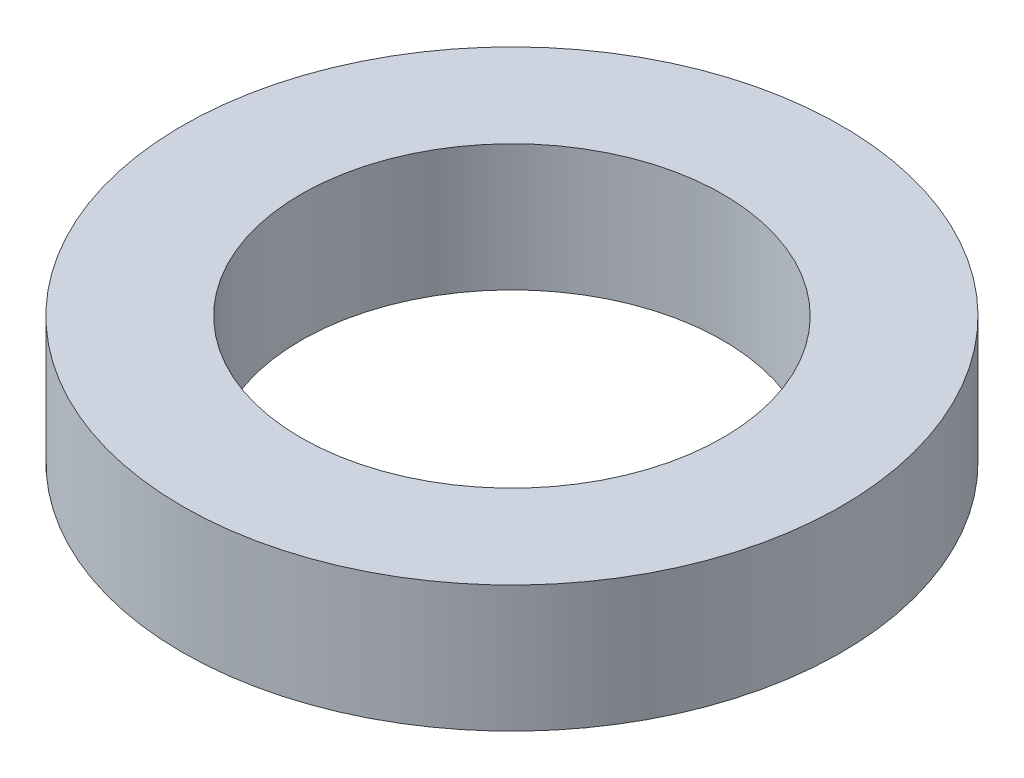
SolidWorks part; units mm, degrees
ref_plane "Front Plane" through (0, 0, 0) normal (0, 0, 1) x (1, 0, 0)
ref_plane "Top Plane" through (0, 0, 0) normal (0, 1, 0) x (1, 0, 0)
ref_plane "Right Plane" through (0, 0, 0) normal (1, 0, 0) x (0, 0, -1)
sketch "Sketch1" plane through (0, 0, 0) normal (0, 1, 0) x (1, 0, 0)
  circle A0 centre (0, 0) radius 62.5
  dimension "FLANGE_OD" = 125
extrude "Boss-Extrude1" add sketch "Sketch1" along normal blind 24
sketch "Sketch2" plane through (0, 0, 0) normal (0, 1, 0) x (1, 0, 0)
  circle A0 centre (0, 0) radius 40
  dimension "BORE_D" = 80
extrude "Cut-Extrude1" cut sketch "Sketch2" along normal through all
sketch "Sketch3" plane through (0, 24, 0) normal (0, 1, 0) x (1, 0, 0)
  circle A0 centre (0, 0) radius 27.8659 construction
  circle A1 centre (-27.8659, 0) radius 3.2676
  dimension "BOLT_D" = 6.5352
  dimension "BOLT_PCD" = 55.7318
extrude "Cut-Extrude2" cut sketch "Sketch3" against normal blind 14.4798 rebuild error yes
pattern_circular "CirPattern1" count 5 over 360 rebuild error yes
